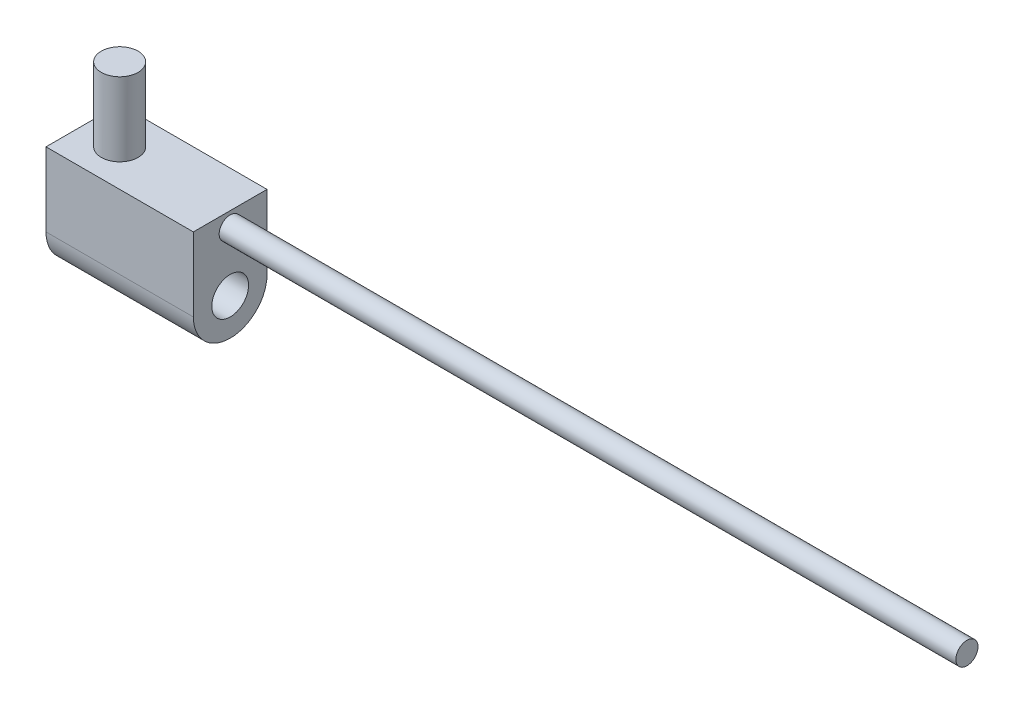
SolidWorks part; units mm, degrees
ref_plane "정면" through (0, 0, 0) normal (0, 0, 1) x (1, 0, 0)
ref_plane "윗면" through (0, 0, 0) normal (0, 1, 0) x (1, 0, 0)
ref_plane "우측면" through (0, 0, 0) normal (1, 0, 0) x (0, 0, -1)
sketch "스케치1" plane through (0, 0, 0) normal (1, 0, 0) x (0, 0, -1)
  line L1 (5, -7.5) -> (-5, -7.5)
  line L2 (5, -7.5) -> (5, 7.5)
  line L3 (5, 7.5) -> (-5, 7.5)
  line L4 (-5, -7.5) -> (-5, 7.5)
  line L5 (5, -7.5) -> (-5, 7.5) construction
  line L6 (5, 7.5) -> (-5, -7.5) construction
  point P0 (0, 0)
  dimension "D1" = 10
  dimension "D2" = 15
extrude "보스-돌출1" add sketch "스케치1" along normal blind 20
fillet "필렛1" 2 edges at (10, -7.5, 5) (10, -7.5, -5) type full round first side face at (10, 0, 5) second side face at (10, 0, -5) middle face at (10, -7.5, 0)
sketch "스케치2" plane through (0, 7.5, 0) normal (0, 1, 0) x (1, 0, 0)
  line L0 (0, 5) -> (0, -5) construction
  circle A0 centre (5, 0) radius 2.5
  dimension "D1" = 5
  dimension "D2" = 5
extrude "보스-돌출2" add sketch "스케치2" along normal blind 10
sketch "스케치3" plane through (20, 0, 0) normal (1, 0, 0) x (0, 0, -1)
  circle A0 centre (0, -2.5) radius 2.5
  dimension "D1" = 5
extrude "컷-돌출1" cut sketch "스케치3" against normal through all
sketch "스케치4" plane through (20, 0, 0) normal (1, 0, 0) x (0, 0, -1)
  line L0 (5, 7.5) -> (-5, 7.5) construction
  circle A0 centre (0, 5.5) radius 1.5
  dimension "D1" = 3
  dimension "D2" = 2
extrude "보스-돌출3" add sketch "스케치4" along normal blind 100
